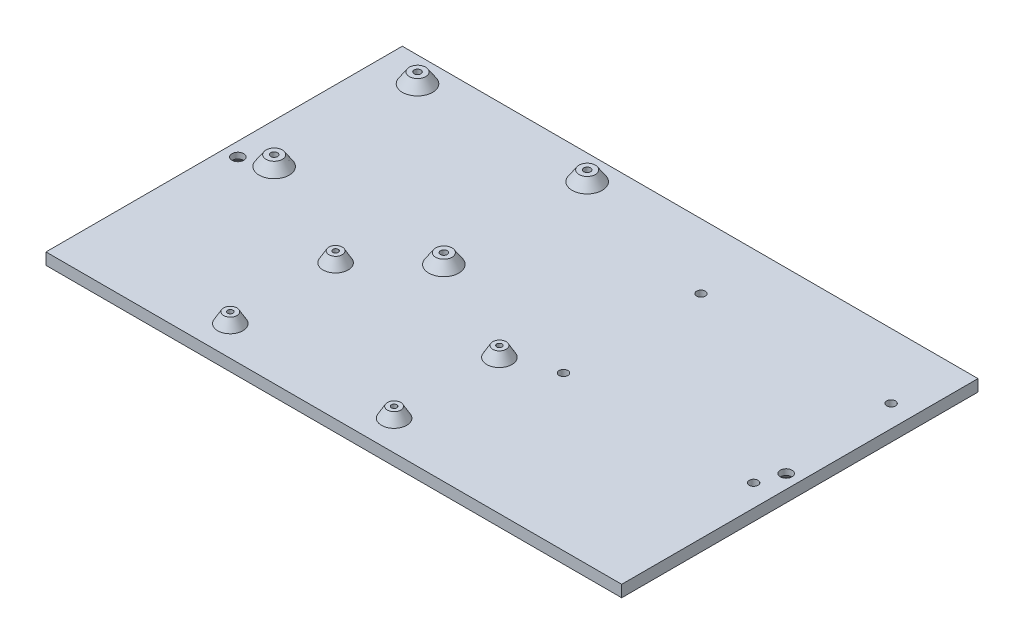
SolidWorks part; units mm, degrees
ref_plane "Front Plane" through (0, 0, 0) normal (0, 0, 1) x (1, 0, 0)
ref_plane "Top Plane" through (0, 0, 0) normal (0, 1, 0) x (1, 0, 0)
ref_plane "Right Plane" through (0, 0, 0) normal (1, 0, 0) x (0, 0, -1)
sketch "Sketch1" plane through (0, 0, 0) normal (0, 1, 0) x (1, 0, 0)
  line L1 (-98.4, 60.9) -> (98.4, 60.9)
  line L2 (-98.4, 60.9) -> (-98.4, -60.9)
  line L3 (-98.4, -60.9) -> (98.4, -60.9)
  line L4 (98.4, 60.9) -> (98.4, -60.9)
  line L5 (-98.4, 60.9) -> (98.4, -60.9) construction
  line L6 (-98.4, -60.9) -> (98.4, 60.9) construction
  point P0 (0, 0)
  dimension "D1" = 121.8
  dimension "D2" = 196.8
extrude "Boss-Extrude1" add sketch "Sketch1" along normal blind 4
sketch "Sketch2" plane through (0, 0, 0) normal (0, -1, 0) x (-1, 0, 0)
  line L0 (98.4, 60.9) -> (98.4, -60.9) construction
  circle A0 centre (93.7, 0) radius 2
  dimension "D2" = 4
  dimension "D1" = 4.7
extrude "Cut-Extrude1" cut sketch "Sketch2" against normal through all and the other way through all
hole_wizard "CSK for M4 Hex Socket Countersunk Head Screw3" positions "3DSketch1" profile "Sketch4" countersink size "M4" standard "DIN" end condition through all
sketch3d "3DSketch1"
  line L0 (-93.7, 4, 0) -> (-93.7, 0, 0) construction
  point P0 (-93.7, 0, 0)
sketch "Sketch4" plane through (-93.7, 0, 0) normal (1, 0, 0) x (0, 0, -1)
  line L0 (0, 0) -> (0, 4)
  line L1 (0, 4) -> (2, 4)
  line L2 (2, 4) -> (2, 2)
  line L3 (2, 2) -> (4, 0)
  line L5 (4, 0) -> (0, 0)
  line L6 (-2, 2) -> (-4, 0) construction
  line L11 (0, -6.35) -> (0, 107.95) construction
  dimension "Thru Hole Dia." = 4
  dimension "Thru Hole Depth" = 4
  dimension "Near C'Sink Dia." = 8
  dimension "Near C'Sink Angle" = 90
mirror "Mirror1" about plane through (0, 0, 0) normal (1, 0, 0) of "CSK for M4 Hex Socket Countersunk Head Screw3", "Cut-Extrude1"
sketch "Sketch6" plane through (0, 4, 0) normal (0, 1, 0) x (1, 0, 0)
  line L4 (98.4, 60.9) -> (-98.4, 60.9) construction
  line L5 (-98.4, 60.9) -> (-98.4, -60.9) construction
  circle A0 centre (-26.7, 3.4) radius 2.75
  circle A1 centre (-84.7, 3.4) radius 2.75
  circle A2 centre (-26.7, 52.4) radius 2.75
  circle A3 centre (-84.7, 52.4) radius 2.75
  line B0 (-88.2, 55.9) -> (-88.2, -0.1) construction
  line B1 (-88.2, -0.1) -> (-0.828, -0.1) construction
  line B2 (-0.828, -0.1) -> (-0.828, 55.9) construction
  line B3 (-0.828, 55.9) -> (-88.2, 55.9) construction
  circle B4 centre (-84.7, 52.4) radius 1.6
  circle B5 centre (-26.7, 52.4) radius 1.6
  circle B6 centre (-84.7, 3.4) radius 1.6
  circle B7 centre (-26.7, 3.4) radius 1.6
  dimension "D3" = 5.5
  dimension "D1" = 5
  dimension "D2" = 10.2
sketch_block_instance "Raspberry_Pi_3-1"
sketch_block "Raspberry_Pi_3" parameters "D11"=3.2, "D1"=87.372, "D2"=56, "D3"=3.5, "D4"=3.5, "D5"=3.5, "D6"=3.5, "D7"=3.5, "D8"=3.5, "D9"=58, "D10"=58
extrude "Boss-Extrude3" add sketch "Sketch6" along normal blind 3.5 contours A2 | A0 | A1 | A3
chamfer "Chamfer1" distance 2.4 angle 56 4 edges at (-84.7, 4, -49.65) (-26.7, 4, -49.65) (-84.7, 4, -0.65) (-26.7, 4, -0.65) first distance on face at (-84.7, 4, -49.65)
sketch "Sketch7" plane through (0, 7.5, 0) normal (0, 1, 0) x (1, 0, 0)
  circle A0 centre (-26.7, 3.4) radius 1.16
  circle A1 centre (-26.7, 52.4) radius 1.16
  circle A2 centre (-84.7, 52.4) radius 1.16
  circle A3 centre (-84.7, 3.4) radius 1.16
  dimension "D1" = 2.32
extrude "Cut-Extrude2" cut sketch "Sketch7" against normal blind 6.5
sketch "Sketch8" plane through (0, 4, 0) normal (0, 1, 0) x (1, 0, 0)
  circle A4 centre (-84.7, 3.4) radius 1.16 construction
  circle A5 centre (-26.7, 3.4) radius 1.16 construction
  circle A6 centre (-45.7, -14.6) radius 2.25
  circle A7 centre (10.3, -14.6) radius 2.25
  circle A8 centre (10.3, -50.6) radius 2.25
  circle A9 centre (-45.7, -50.6) radius 2.25
  circle B0 centre (-45.7, -50.6) radius 1
  circle B1 centre (-45.7, -14.6) radius 1
  circle B2 centre (10.3, -50.6) radius 1
  circle B3 centre (10.3, -14.6) radius 1
  line B4 (-47.7, -52.6) -> (-47.7, -12.6)
  line B5 (-47.7, -52.6) -> (12.3, -52.6)
  line B6 (-47.7, -12.6) -> (12.3, -12.6)
  line B7 (12.3, -52.6) -> (12.3, -12.6)
  line B8 (-47.7, -52.6) -> (12.3, -12.6) construction
  line B9 (12.3, -52.6) -> (-47.7, -12.6) construction
  dimension "D3" = 4.5
  dimension "D1" = 16
  dimension "D2" = 37
sketch_block_instance "Block1-1"
sketch_block "Block1" parameters "D3"=2, "D1"=36, "D2"=56, "D4"=27.8378, "D5"=16.8829, "D6"=53.5192, "D7"=78.3779
extrude "Boss-Extrude4" add sketch "Sketch8" along normal blind 3.5 contours A9 | A6 | A7 | A8
chamfer "Chamfer2" distance 2.05 angle 60 4 edges at (10.3, 4, 16.85) (10.3, 4, 52.85) (-45.7, 4, 52.85) (-45.7, 4, 16.85) first distance on face at (10.3, 4, 52.85)
sketch "Sketch9" plane through (0, 7.5, 0) normal (0, 1, 0) x (1, 0, 0)
  circle A0 centre (-45.7, -14.6) radius 0.93
  circle A1 centre (10.3, -14.6) radius 0.93
  circle A2 centre (10.3, -50.6) radius 0.93
  circle A3 centre (-45.7, -50.6) radius 0.93
  dimension "D1" = 1.86
extrude "Cut-Extrude3" cut sketch "Sketch9" against normal blind 6.5
sketch "Sketch10" plane through (0, 4, 0) normal (0, 1, 0) x (1, 0, 0)
  line L0 (98.4, 60.9) -> (-98.4, 60.9) construction
  line L1 (89.4, 60.7) -> (27.4, 60.7)
  line L2 (89.4, 60.7) -> (89.4, -30.3)
  line L3 (89.4, -30.3) -> (27.4, -30.3)
  line L4 (27.4, 60.7) -> (27.4, -30.3)
  line L5 (98.4, -60.9) -> (98.4, 60.9) construction
  circle A0 centre (25.9, 38.7) radius 1.5
  circle A1 centre (25.9, -8.3) radius 1.5
  circle A2 centre (90.9, -8.3) radius 1.5
  circle A3 centre (90.9, 38.7) radius 1.5
  point P16 (0, 0)
  point P17 (0, 0)
  point P18 (0, 0)
  point P19 (0, 0)
  point P20 (0, 0)
  dimension "D5" = 3
  dimension "D1" = 62
  dimension "D2" = 91
  dimension "D3" = 0.2
  dimension "D4" = 9
  dimension "D6" = 22
  dimension "D7" = 22
extrude "Cut-Extrude4" cut sketch "Sketch10" against normal through all contours A0 | A1 | A2 | A3 region at (90.9, 4, -38.7) region at (90.9, 4, 8.3) region at (25.9, 4, 8.3) region at (25.9, 4, -38.7)
